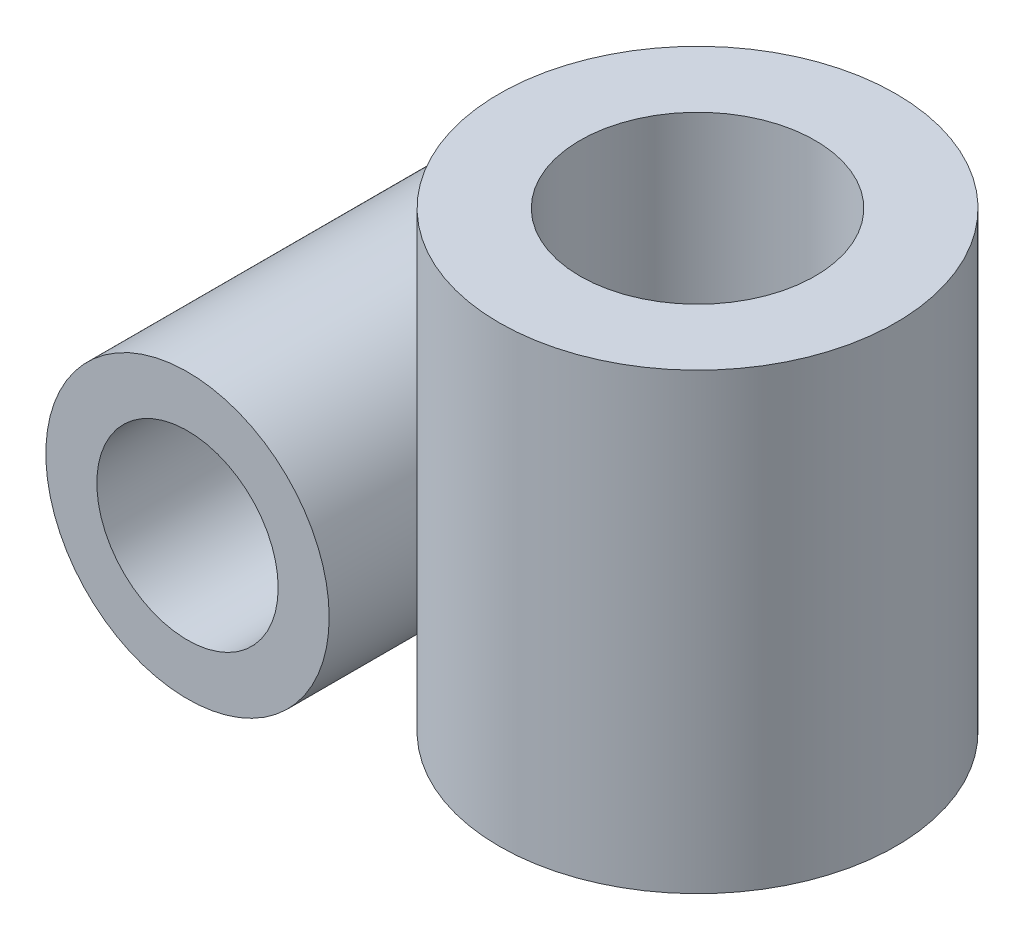
SolidWorks part; units mm, degrees
ref_plane "Front Plane" through (0, 0, 0) normal (0, 0, 1) x (1, 0, 0)
ref_plane "Top Plane" through (0, 0, 0) normal (0, 1, 0) x (1, 0, 0)
ref_plane "Right Plane" through (0, 0, 0) normal (1, 0, 0) x (0, 0, -1)
sketch "Sketch3" plane through (0, 0, 0) normal (0, 1, 0) x (1, 0, 0)
  circle A0 centre (0, 0) radius 4.15
  circle A1 centre (0, 0) radius 7
  dimension "D1" = 8.3
  dimension "D2" = 14
extrude "Boss-Extrude1" add sketch "Sketch3" along normal blind 16
sketch "Sketch4" plane through (0, 0, 0) normal (0, 0, 1) x (1, 0, 0)
  line L0 (-7, 16) -> (-7, 0) construction
  line L1 (-7, 16) -> (-7, 0) construction
  line L2 (-7, 0) -> (7, 0) construction
  circle A0 centre (-10, 5) radius 3.2
  circle A1 centre (-10, 5) radius 5
  point P6 (0, 0)
  dimension "D2" = 10
  dimension "D3" = 6.4
  dimension "D1" = 3
extrude "Boss-Extrude2" add sketch "Sketch4" along normal mid plane 16
extrude "Cut-Extrude1" cut sketch "Sketch4<2>" against normal through all both and the other way through all contours L1 A0 | A0 L1 region at (-6.9198, 5, 0) region at (-10.0289, 5, 0)
sketch "Sketch4<2>" plane through (0, 0, 0) normal (0, 0, 1) x (1, 0, 0) same geometry as "Sketch4"
